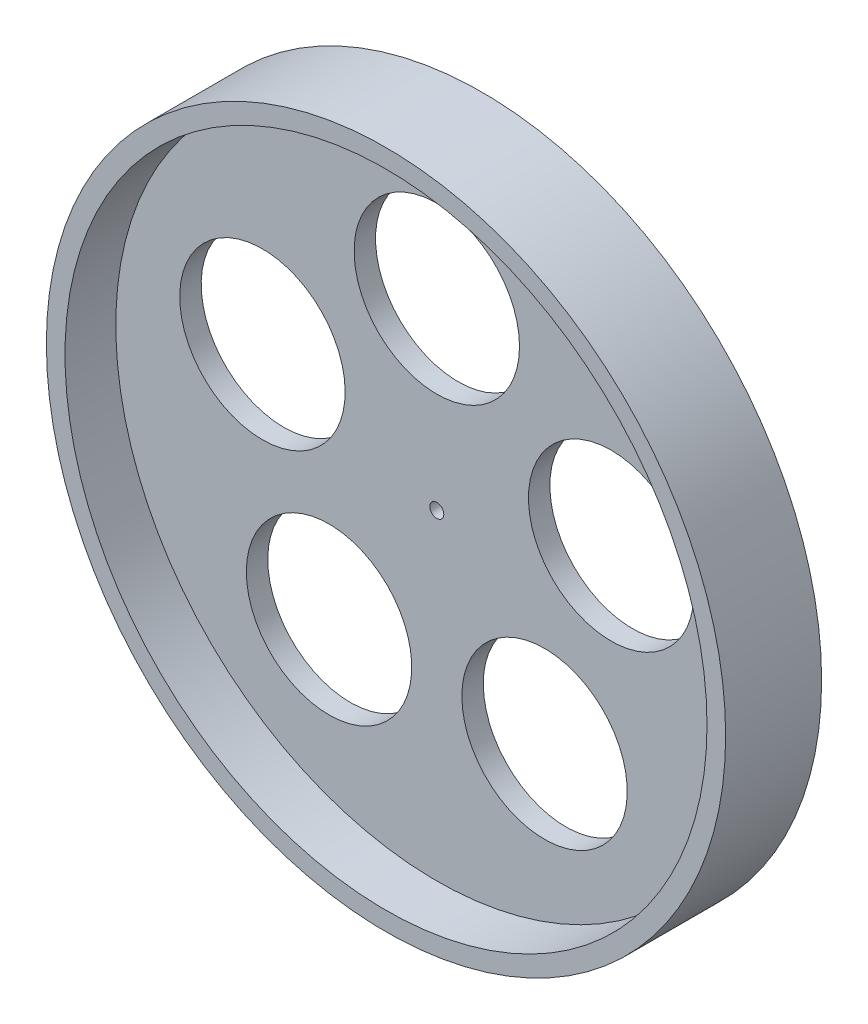
SolidWorks part; units mm, degrees
ref_plane "Front Plane" through (0, 0, 0) normal (0, 0, 1) x (1, 0, 0)
ref_plane "Top Plane" through (0, 0, 0) normal (0, 1, 0) x (1, 0, 0)
ref_plane "Right Plane" through (0, 0, 0) normal (1, 0, 0) x (0, 0, -1)
ref_axis "X-Axis" through (-88.99, 0, 0) along (1, 0, 0)
ref_axis "Y-Axis" through (0, 55, 0) along (0, -1, 0)
ref_axis "Z-Axis" through (0, 0, -88.99) along (0, 0, 1)
sketch "Sketch1" plane through (0, 0, 0) normal (0, 0, 1) x (1, 0, 0)
  circle A0 centre (0, 0) radius 68.9
  dimension "D1" = 137.8
extrude "Boss-Extrude1" add sketch "Sketch1" along normal mid plane 4.6
sketch "Sketch2" plane through (0, 0, 2.3) normal (0, 0, 1) x (1, 0, 0)
  line L0 (0, 0) -> (0, 39.35) construction
  line L1 (0, 39.35) -> (0, 68.9) construction
  circle A0 centre (0, 39.35) radius 17.75
  circle A1 centre (0, 0) radius 68.9 construction
  point P8 (0, 57.1)
  dimension "D1" = 35.5
  dimension "D2" = 11.8
extrude "Cut-Extrude1" cut sketch "Sketch2" against normal through all
pattern_circular "CirPattern1" count 5 over 360 about axis through (0, 0, -88.99) along (0, 0, 1) of "Cut-Extrude1"
sketch "Sketch3" plane through (0, 0, 2.3) normal (0, 0, 1) x (1, 0, 0)
  circle A1 centre (0, 0) radius 72.9
  circle A2 centre (0, 0) radius 68.9
  circle A3 centre (0, 0) radius 68.9
  dimension "D1" = 0
  dimension "D2" = 4
extrude "Boss-Extrude2" add sketch "Sketch3" along normal blind 10.9 and the other way blind 9.7
sketch "Sketch4" plane through (0, 0, -2.3) normal (0, 0, -1) x (-1, 0, 0)
  circle A0 centre (0, 0) radius 11.65
  dimension "D1" = 23.3
extrude "Boss-Extrude3" add sketch "Sketch4" along normal blind 8
sketch "Sketch6" plane through (0, 0, 2.3) normal (0, 0, 1) x (1, 0, 0)
  circle A0 centre (0, 0) radius 1.5
  dimension "D1" = 3
extrude "Cut-Extrude2" cut sketch "Sketch6" against normal through all
